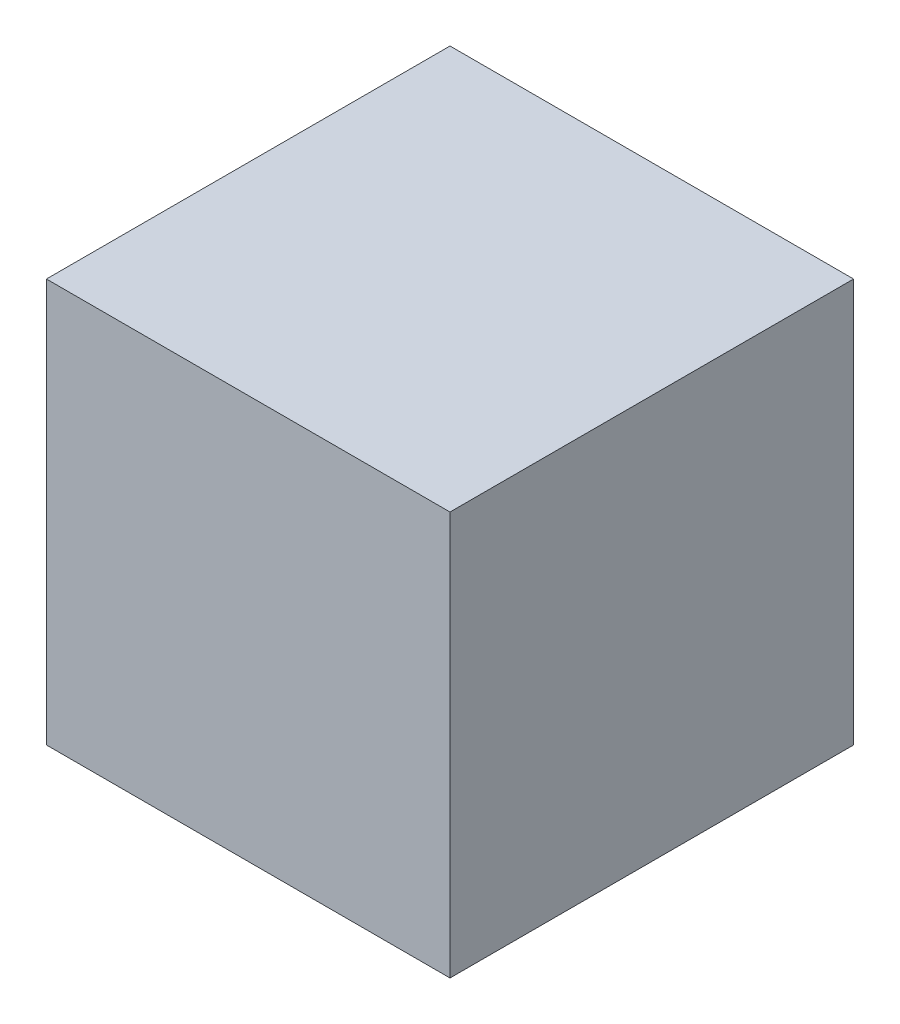
SolidWorks part; units mm, degrees
ref_plane "Front Plane" through (0, 0, 0) normal (0, 0, 1) x (1, 0, 0)
ref_plane "Top Plane" through (0, 0, 0) normal (0, 1, 0) x (1, 0, 0)
ref_plane "Right Plane" through (0, 0, 0) normal (1, 0, 0) x (0, 0, -1)
sketch "Sketch1" plane through (0, 0, 0) normal (0, 1, 0) x (1, 0, 0)
  line L1 (-101.6, -101.6) -> (101.6, -101.6)
  line L2 (-101.6, -101.6) -> (-101.6, 101.6)
  line L3 (-101.6, 101.6) -> (101.6, 101.6)
  line L4 (101.6, -101.6) -> (101.6, 101.6)
  line L5 (-101.6, -101.6) -> (101.6, 101.6) construction
  line L6 (-101.6, 101.6) -> (101.6, -101.6) construction
  point P0 (0, 0)
  dimension "D1" = 203.2
  dimension "D2" = 203.2
extrude "Boss-Extrude1" add sketch "Sketch1" along normal blind 203.2
sketch "Sketch2" plane through (0, 0, 0) normal (0, 1, 0) x (1, 0, 0)
  line L1 (-46.5, -39) -> (46.5, -39)
  line L2 (-46.5, -39) -> (-46.5, 39)
  line L3 (-46.5, 39) -> (46.5, 39)
  line L4 (46.5, -39) -> (46.5, 39)
  line L5 (-46.5, -39) -> (46.5, 39) construction
  line L6 (-46.5, 39) -> (46.5, -39) construction
  point P0 (0, 0)
  point P5 (0, 0)
  dimension "D1" = 93
  dimension "D2" = 78
extrude "Boss-Extrude2" add sketch "Sketch2" along normal blind 20.32 separate body
sketch "Sketch3" plane through (0, 0, 0) normal (0, 0, 1) x (1, 0, 0)
  line L0 (-46.2856, 0) -> (-64.0104, 42.1232)
  line L1 (-101.6, 0) -> (101.6, 0) construction
  line L2 (-64.0104, 42.1232) -> (62.1776, 42.1232)
  line L3 (62.1776, 42.1232) -> (46.7293, 0)
  line L4 (-34.3221, 42.1232) -> (-64.0104, 107.3189)
  line L5 (37.0218, 42.1232) -> (67.4398, 107.3189)
  line L6 (-39.8718, 196.3658) -> (-97.9949, 183.1688)
  line L7 (-97.9949, 183.1688) -> (-73.8471, 94.4399)
  line L8 (-73.8471, 94.4399) -> (-81.99, 154.2477)
  line L9 (-81.99, 154.2477) -> (-39.8718, 196.3658)
  ellipse E0 centre (3.6973, 137.7453) end of major axis (-77.9687, 135.3176) minor radius 60.5946
  point P17 (-49.6994, 192.4348)
  point P19 (-98.2757, 169.4102)
  point P22 (-82.2708, 144.9817)
  point P23 (-73.8471, 94.4399)
  point P24 (-39.8718, 196.3658)
  point P25 (-81.7092, 147.228)
  point P26 (-97.9949, 183.1688)
  point P27 (-81.99, 154.2477)
